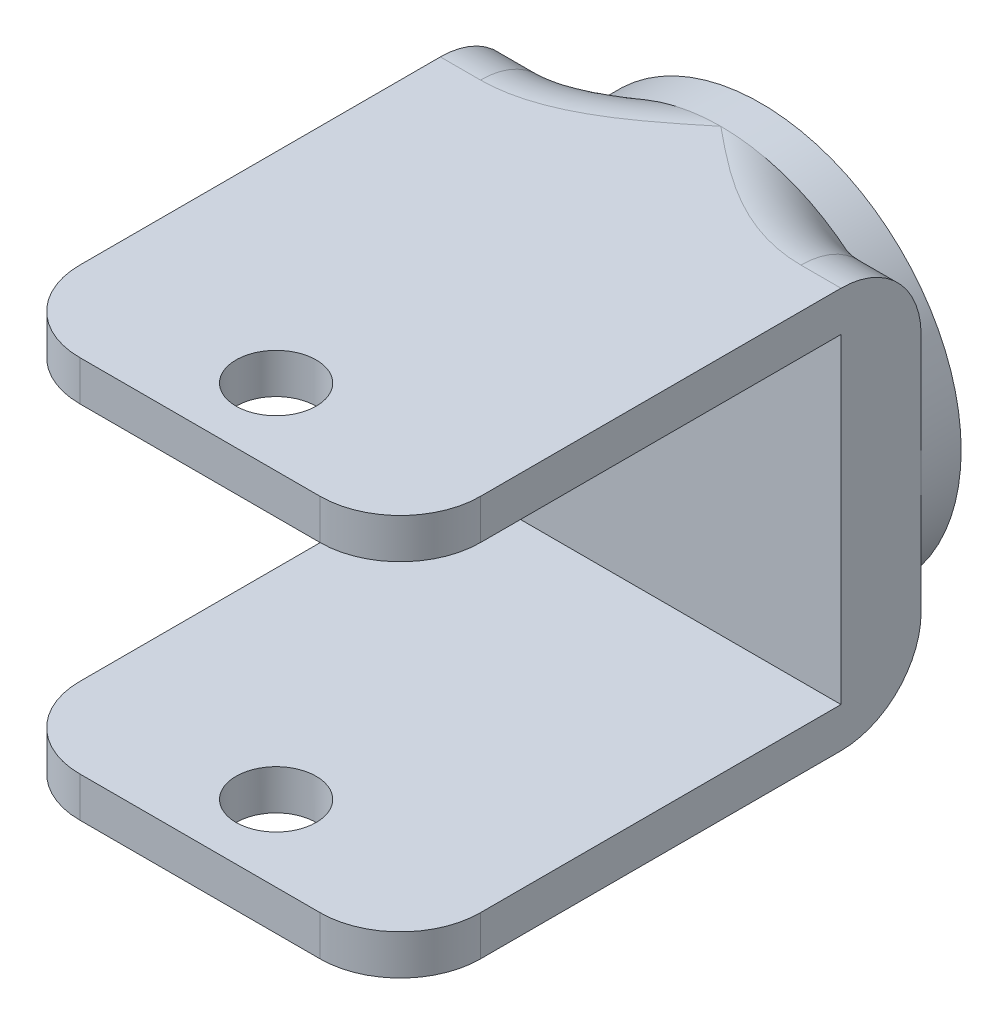
SolidWorks part; units mm, degrees
ref_plane "Front Plane" through (0, 0, 0) normal (0, 0, 1) x (1, 0, 0)
ref_plane "Top Plane" through (0, 0, 0) normal (0, 1, 0) x (1, 0, 0)
ref_plane "Right Plane" through (0, 0, 0) normal (1, 0, 0) x (0, 0, -1)
sketch "Sketch1" plane through (0, 0, 0) normal (0, 0, 1) x (1, 0, 0)
  line L1 (-25, 25) -> (25, 25)
  line L2 (-25, 25) -> (-25, -25)
  line L3 (-25, -25) -> (25, -25)
  line L4 (25, 25) -> (25, -25)
  line L5 (-25, 25) -> (25, -25) construction
  line L6 (-25, -25) -> (25, 25) construction
  point P0 (0, 0)
  dimension "D1" = 50
  dimension "D2" = 50
extrude "Boss-Extrude1" add sketch "Sketch1" along normal blind 10 contours L2 L1 L4 L3
sketch "Sketch2" plane through (0, 0, 0) normal (0, 0, -1) x (-1, 0, 0)
  circle A0 centre (0, 0) radius 25
extrude "Boss-Extrude2" add sketch "Sketch2" along normal blind 5 contours A0
sketch "Sketch3" plane through (0, 0, -5) normal (0, 0, -1) x (-1, 0, 0)
  circle A0 centre (0, 0) radius 5
extrude "Boss-Extrude3" add sketch "Sketch3" along normal blind 5 contours A0
sketch "Sketch4" plane through (0, 0, 10) normal (0, 0, 1) x (1, 0, 0)
  line L0 (25, 25) -> (25, -25) construction
  line L1 (-25, 25) -> (25, 25)
  line L2 (-25, 25) -> (-25, 20)
  line L3 (-25, 20) -> (25, 20)
  line L4 (25, 25) -> (25, 20)
  line L6 (-25, -25) -> (25, -25)
  line L7 (-25, -25) -> (-25, -20)
  line L8 (-25, -20) -> (25, -20)
  line L9 (25, -25) -> (25, -20)
  dimension "D1" = 5
  dimension "D2" = 5
extrude "Boss-Extrude4" add sketch "Sketch4" along normal blind 55
sketch "Sketch5" plane through (0, 25, 0) normal (0, 1, 0) x (1, 0, 0)
  line L0 (0, 0) -> (0, -55.5) construction
  circle A0 centre (0, -55.5) radius 5
extrude "Cut-Extrude1" cut sketch "Sketch5" against normal blind 50
fillet "Fillet1" radius 10 4 edges at (25, -22.5, 65) (25, 22.5, 65) (-25, -22.5, 65) (-25, 22.5, 65)
fillet "Fillet2" radius 10 4 edges at (12.5, 25, 0) (12.5, -25, 0) (-12.5, 25, 0) (-12.5, -25, 0)
